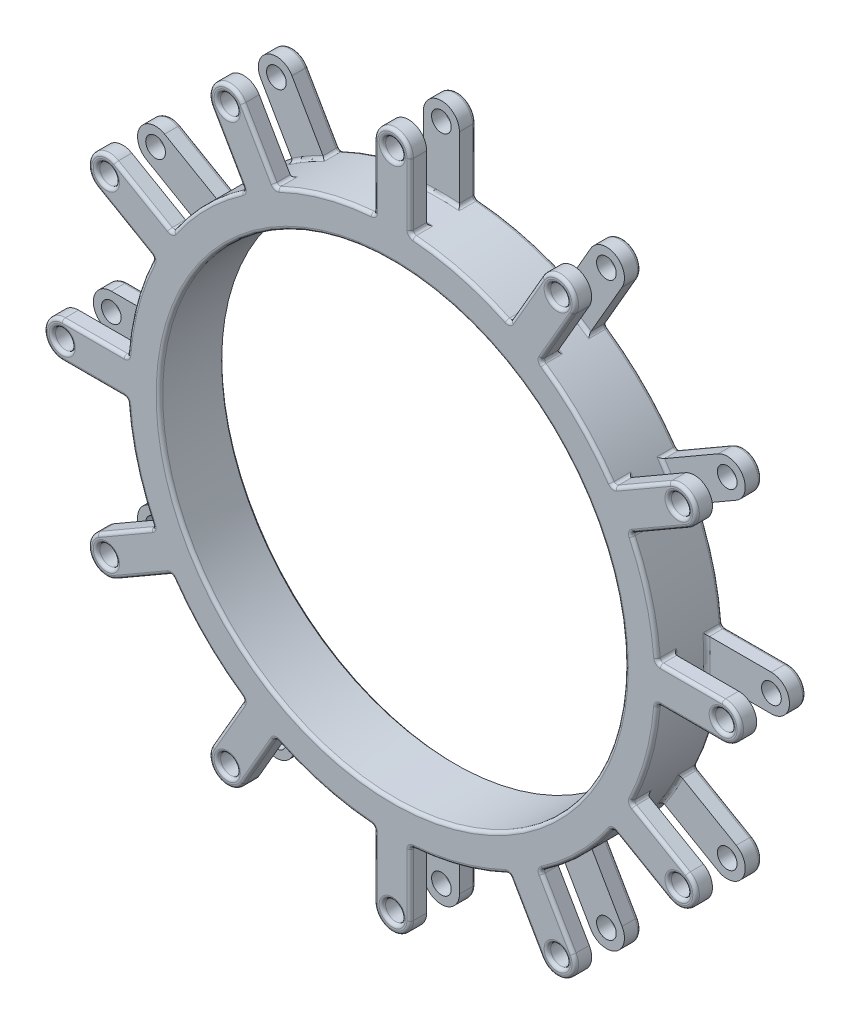
SolidWorks part; units mm, degrees
ref_plane "Plan de face" through (0, 0, 0) normal (0, 0, 1) x (1, 0, 0)
ref_plane "Plan de dessus" through (0, 0, 0) normal (0, 1, 0) x (1, 0, 0)
ref_plane "Plan de droite" through (0, 0, 0) normal (1, 0, 0) x (0, 0, -1)
sketch "Esquisse1" plane through (0, 0, 0) normal (0, 0, 1) x (1, 0, 0)
  circle A0 centre (0, 0) radius 35.5
  circle A1 centre (0, 0) radius 40.5
  dimension "D1" = 71
  dimension "D2" = 5
extrude "Boss.-Extru.1" add sketch "Esquisse1" along normal blind 10
sketch "Esquisse2" plane through (0, 0, 0) normal (0, 0, -1) x (-1, 0, 0)
  line L0 (-64.4753, 0) -> (79.2775, 0) construction
  line L1 (0, 72.5747) -> (0, -74.9925) construction
  line L2 (-40.4065, 2.75) -> (-50.3253, 2.75)
  line L3 (-40.4065, -2.75) -> (-50.3253, -2.75)
  arc A0 (-50.3253, -2.75) -> (-50.3253, 2.75) centre (-50.3253, 0) cw
  circle A1 centre (0, 0) radius 40.5
  circle A2 centre (0, 0) radius 40.5
  circle A3 centre (-50.3253, 0) radius 1.5
  point P83 (-1.2528, -4.6755)
  dimension "D3" = 3
  dimension "D2" = 2.75
  dimension "D1" = 0
extrude "Boss.-Extru.2" add sketch "Esquisse2" against normal blind 2.5
ref_plane "Plan2" through (0, 0, 5) normal (0, 0, -1) x (-1, 0, 0)
mirror "Symétrie1" about plane through (0, 0, 5) normal (0, 0, -1) of "Boss.-Extru.2"
chamfer "Chanfrein1" distance 0.5 angle 45 1 edges at (35.5, 0, 0)
pattern_circular "Répétition circulaire2" count 12 over 360 about axis through (0, 0, 0) along (0, 0, 1) of "Boss.-Extru.2", "Symétrie1"
fillet "Congé2" radius 0.5 194 edges at (-28.6378, 28.6378, 0) (-26.5376, 45.9645, 0) (-22.5848, 33.6181, 1.25) (-24.4126, 42.2839, 0) (-20.3014, 40.663, 0) (-17.8217, 36.3681, 1.25) (-20.25, 35.074, 2.5) (-25.0645, 37.913, 0) (53.0753, 0, 0) (-39.12, 10.4822, 0) (-45.9645, 26.5376, 0) (-36.3681, 17.8217, 1.25) (-42.2839, 24.4126, 0) (-37.913, 25.0645, 0) (-33.6181, 22.5848, 1.25) (-35.074, 20.25, 2.5) (-40.663, 20.3014, 0) (40.4065, 2.75, 1.25) (48.8253, 0, 0) (45.3659, -2.75, 0) (40.4065, -2.75, 1.25) (-39.12, -10.4822, 0) (-53.0753, 0, 0) (-40.4065, -2.75, 1.25) (-48.8253, 0, 0) (-45.3659, 2.75, 0) (-40.4065, 2.75, 1.25) (-40.5, 0, 2.5) (-45.3659, -2.75, 0) (40.5, 0, 2.5) (45.3659, 2.75, 0) (-28.6378, -28.6378, 0) (-45.9645, -26.5376, 0) (-33.6181, -22.5848, 1.25) (-42.2839, -24.4126, 0) (-40.663, -20.3014, 0) (-36.3681, -17.8217, 1.25) (-35.074, -20.25, 2.5) (-37.913, -25.0645, 0) (-10.4822, -39.12, 0) (-26.5376, -45.9645, 0) (-17.8217, -36.3681, 1.25) (-24.4126, -42.2839, 0) (-25.0645, -37.913, 0) (-22.5848, -33.6181, 1.25) (-20.25, -35.074, 2.5) (-20.3014, -40.663, 0) (10.4822, -39.12, 0) (0, -53.0753, 0) (2.75, -40.4065, 1.25) (0, -48.8253, 0) (-2.75, -45.3659, 0) (-2.75, -40.4065, 1.25) (0, -40.5, 2.5) (2.75, -45.3659, 0) (39.12, 10.4822, 0) (28.6378, -28.6378, 0) (26.5376, -45.9645, 0) (22.5848, -33.6181, 1.25) (24.4126, -42.2839, 0) (20.3014, -40.663, 0) (17.8217, -36.3681, 1.25) (20.25, -35.074, 2.5) (25.0645, -37.913, 0) (39.12, -10.4822, 0) (45.9645, -26.5376, 0) (36.3681, -17.8217, 1.25) (42.2839, -24.4126, 0) (37.913, -25.0645, 0) (33.6181, -22.5848, 1.25) (35.074, -20.25, 2.5) (40.663, -20.3014, 0) (28.6378, 28.6378, 10) (35.074, 20.25, 7.5) (36.3681, 17.8217, 8.75) (37.913, 25.0645, 10) (33.6181, 22.5848, 8.75) (42.2839, 24.4126, 10) (45.9645, 26.5376, 10) (40.663, 20.3014, 10) (10.4822, 39.12, 10) (20.25, 35.074, 7.5) (22.5848, 33.6181, 8.75) (20.3014, 40.663, 10) (17.8217, 36.3681, 8.75) (24.4126, 42.2839, 10) (26.5376, 45.9645, 10) (25.0645, 37.913, 10) (-10.4822, 39.12, 10) (0, 40.5, 7.5) (2.75, 40.4065, 8.75) (-2.75, 45.3659, 10) (-2.75, 40.4065, 8.75) (0, 48.8253, 10) (0, 53.0753, 10) (2.75, 45.3659, 10) (-28.6378, 28.6378, 10) (-20.25, 35.074, 7.5) (-17.8217, 36.3681, 8.75) (-25.0645, 37.913, 10) (-22.5848, 33.6181, 8.75) (-24.4126, 42.2839, 10) (-26.5376, 45.9645, 10) (-20.3014, 40.663, 10) (40.5, 0, 7.5) (-39.12, 10.4822, 10) (-35.074, 20.25, 7.5) (-33.6181, 22.5848, 8.75) (40.4065, -2.75, 8.75) (-40.663, 20.3014, 10) (-36.3681, 17.8217, 8.75) (-42.2839, 24.4126, 10) (-45.9645, 26.5376, 10) (-37.913, 25.0645, 10) (45.3659, 2.75, 10) (40.4065, 2.75, 8.75) (48.8253, 0, 10) (-39.12, -10.4822, 10) (53.0753, 0, 10) (-40.5, 0, 7.5) (-40.4065, 2.75, 8.75) (-45.3659, -2.75, 10) (-40.4065, -2.75, 8.75) (-48.8253, 0, 10) (-53.0753, 0, 10) (-45.3659, 2.75, 10) (45.3659, -2.75, 10) (-28.6378, -28.6378, 10) (-35.074, -20.25, 7.5) (-36.3681, -17.8217, 8.75) (-37.913, -25.0645, 10) (-33.6181, -22.5848, 8.75) (-42.2839, -24.4126, 10) (-45.9645, -26.5376, 10) (-40.663, -20.3014, 10) (-10.4822, -39.12, 10) (-20.25, -35.074, 7.5) (-22.5848, -33.6181, 8.75) (-20.3014, -40.663, 10) (-17.8217, -36.3681, 8.75) (-24.4126, -42.2839, 10) (-26.5376, -45.9645, 10) (-25.0645, -37.913, 10) (10.4822, -39.12, 10) (0, -40.5, 7.5) (-2.75, -40.4065, 8.75) (2.75, -45.3659, 10) (2.75, -40.4065, 8.75) (0, -48.8253, 10) (0, -53.0753, 10) (-2.75, -45.3659, 10) (28.6378, -28.6378, 10) (20.25, -35.074, 7.5) (17.8217, -36.3681, 8.75) (25.0645, -37.913, 10) (22.5848, -33.6181, 8.75) (24.4126, -42.2839, 10) (26.5376, -45.9645, 10) (20.3014, -40.663, 10) (39.12, -10.4822, 10) (35.074, -20.25, 7.5) (33.6181, -22.5848, 8.75) (40.663, -20.3014, 10) (36.3681, -17.8217, 8.75) (42.2839, -24.4126, 10) (45.9645, -26.5376, 10) (37.913, -25.0645, 10) (39.12, 10.4822, 10) (36, 0, 0) (35.5, 0, 10) (28.6378, 28.6378, 0) (45.9645, 26.5376, 0) (33.6181, 22.5848, 1.25) (42.2839, 24.4126, 0) (40.663, 20.3014, 0) (36.3681, 17.8217, 1.25) (35.074, 20.25, 2.5) (37.913, 25.0645, 0) (10.4822, 39.12, 0) (26.5376, 45.9645, 0) (17.8217, 36.3681, 1.25) (24.4126, 42.2839, 0) (25.0645, 37.913, 0) (22.5848, 33.6181, 1.25) (20.25, 35.074, 2.5) (20.3014, 40.663, 0) (-10.4822, 39.12, 0) (0, 53.0753, 0) (-2.75, 40.4065, 1.25) (0, 48.8253, 0) (2.75, 45.3659, 0) (2.75, 40.4065, 1.25) (0, 40.5, 2.5) (-2.75, 45.3659, 0)
